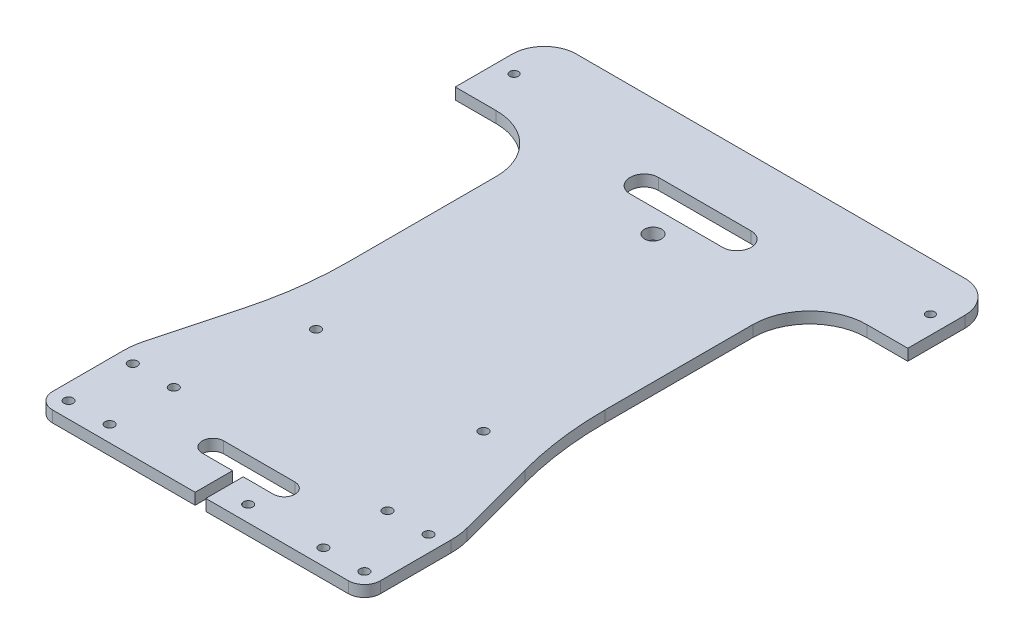
SolidWorks part; units mm, degrees
material "Acrylic (Medium-high impact)"
ref_plane "Front" through (0, 0, 0) normal (0, 0, 1) x (1, 0, 0)
ref_plane "Top" through (0, 0, 0) normal (0, 1, 0) x (1, 0, 0)
ref_plane "Right" through (0, 0, 0) normal (1, 0, 0) x (0, 0, -1)
ref_axis "X" through (-80.9, 0, 0) along (1, 0, 0)
ref_axis "Y" through (0, -50, 0) along (0, 1, 0)
ref_axis "Z" through (0, 0, -80.9) along (0, 0, 1)
sketch "Sketch1" plane through (0, 0, 0) normal (0, 1, 0) x (1, 0, 0)
  line L0 (-46, -160) -> (46, -160)
  line L1 (-46, -160) -> (-46, -133)
  line L2 (-46, -133) -> (-36, -95.6795)
  line L3 (-36, -95.6795) -> (-36, -25)
  line L4 (-36, -25) -> (-63.5, -25)
  line L5 (-63.5, -25) -> (-63.5, 0)
  line L6 (-63.5, 0) -> (63.5, 0)
  line L7 (63.5, 0) -> (63.5, -25)
  line L8 (63.5, -25) -> (36, -25)
  line L9 (36, -25) -> (36, -95.6795)
  line L10 (36, -95.6795) -> (46, -133)
  line L11 (46, -133) -> (46, -160)
  line L12 (0, -160) -> (0, 0) construction
  dimension "D1" = 92
  dimension "D2" = 72
  dimension "D3" = 27
  dimension "D4" = 15
  dimension "D5" = 25
  dimension "D6" = 127
  dimension "D7" = 160
extrude "Boss-Extrude1" add sketch "Sketch1" along normal mid plane 3.175
hole_wizard "M2 Clearance Hole1" positions "Sketch2" profile "Sketch3" hole size "M2" standard "ANSI Metric" end condition up to next
sketch "Sketch2" plane through (0, 1.5875, 0) normal (0, 1, 0) x (1, 0, 0)
  line L0 (-41.5, -155.5) -> (41.5, -155.5) construction
  line L2 (-46, -160) -> (46, -160) construction
  line L3 (-46, -133) -> (-46, -160) construction
  line L4 (46, -160) -> (46, -133) construction
  line L5 (-41.5, -137.5) -> (-41.5, -155.5) construction
  line L8 (41.5, -137.5) -> (41.5, -155.5) construction
  line L9 (-41.5, -137.5) -> (-30, -137.5) construction
  line L10 (-30, -137.5) -> (-30, -155.5) construction
  line L13 (41.5, -137.5) -> (30, -137.5) construction
  line L14 (30, -137.5) -> (30, -155.5) construction
  point P0 (-41.5, -155.5)
  point P2 (41.5, -155.5)
  point P15 (-41.5, -137.5)
  point P17 (41.5, -137.5)
  point P25 (-30, -137.5)
  point P27 (-30, -155.5)
  point P29 (30, -137.5)
  point P31 (30, -155.5)
  dimension "D1" = 4.5
  dimension "D2" = 4.5
  dimension "D3" = 4.5
  dimension "D4" = 18
  dimension "D5" = 60
sketch "Sketch3" plane through (-41.5, 1.5875, 155.5) normal (1, 0, 0) x (0, 0, 1)
  line L0 (0, 0) -> (0, 3.175)
  line L1 (0, 3.175) -> (1.3, 3.175)
  line L2 (1.3, 3.175) -> (1.3, 0)
  line L5 (1.3, 0) -> (0, 0)
  line L11 (0, -6.35) -> (0, 107.95) construction
  dimension "Thru Hole Dia." = 2.6
  dimension "Thru Hole Depth" = 3.175
fillet "Fillet1" radius 4.5 2 edges at (46, 0, 160) (-46, 0, 160)
sketch "Sketch4" plane through (0, 1.5875, 0) normal (0, 1, 0) x (1, 0, 0)
  line L0 (-1.5, -160) -> (-1.5, -149.5)
  line L1 (-41.5, -160) -> (41.5, -160) construction
  line L2 (1.5, -160) -> (1.5, -149.5)
  line L3 (0, 0) -> (0, -146.5) construction
  line L4 (63.5, 0) -> (-63.5, 0) construction
  line L5 (-41.5, -137.5) -> (-41.5, -155.5) construction
  line L6 (-41.5, -146.5) -> (0, -146.5) construction
  line L7 (-1.5, -160) -> (1.5, -160)
  line L8 (-10, -146.5) -> (10, -146.5) construction
  line L9 (-10, -143.5) -> (10, -143.5)
  line L10 (-10, -149.5) -> (-1.5, -149.5)
  line L11 (1.5, -149.5) -> (10, -149.5)
  arc A1 (-10, -143.5) -> (-10, -149.5) centre (-10, -146.5) ccw
  arc A2 (10, -149.5) -> (10, -143.5) centre (10, -146.5) ccw
  point P17 (0, -146.5)
  dimension "D2" = 3
  dimension "D1" = 3
  dimension "D3" = 20
extrude "Cut-Extrude1" cut sketch "Sketch4" against normal up to next
hole_wizard "M2 Clearance Hole3" positions "Sketch5" profile "Sketch6" hole size "M2" standard "ANSI Metric" end condition up to next
sketch "Sketch5" plane through (0, 1.5875, 0) normal (0, 1, 0) x (1, 0, 0)
  line L0 (-24.13, -104.7) -> (24.13, -104.7) construction
  line L2 (-24.13, -104.7) -> (-24.13, -103.43) construction
  line L4 (8.89, -155.5) -> (8.89, -104.7) construction
  line L6 (0, -104.7) -> (0, 0) construction
  line L7 (63.5, 0) -> (-63.5, 0) construction
  line L9 (1.5, -160) -> (41.5, -160) construction
  point P2 (24.13, -104.7)
  point P4 (8.89, -155.5)
  point P20 (-24.13, -103.43)
  dimension "D1" = 48.26
  dimension "D2" = 1.27
  dimension "D3" = 15.24
  dimension "D4" = 50.8
  dimension "D5" = 4.5
sketch "Sketch6" plane through (24.13, 1.5875, 104.7) normal (1, 0, 0) x (0, 0, 1)
  line L0 (0, 0) -> (0, 3.175)
  line L1 (0, 3.175) -> (1.3, 3.175)
  line L2 (1.3, 3.175) -> (1.3, 0)
  line L5 (1.3, 0) -> (0, 0)
  line L11 (0, -6.35) -> (0, 107.95) construction
  dimension "Thru Hole Dia." = 2.6
  dimension "Thru Hole Depth" = 3.175
fillet "Fillet2" radius 9 2 edges at (63.5, 0, 0) (-63.5, 0, 0)
hole_wizard "M2 Clearance Hole2" positions "Sketch7" profile "Sketch8" hole size "M2" standard "ANSI Metric" end condition up to next
sketch "Sketch7" plane through (0, 1.5875, 0) normal (0, 1, 0) x (1, 0, 0)
  line L0 (-58.42, -13.57) -> (58.42, -13.57) construction
  line L2 (0, 0) -> (0, -13.57) construction
  line L3 (54.5, 0) -> (-54.5, 0) construction
  line L5 (-63.5, -25) -> (-36, -25) construction
  point P0 (-58.42, -13.57)
  point P2 (58.42, -13.57)
  dimension "D1" = 116.84
  dimension "D2" = 11.43
sketch "Sketch8" plane through (-58.42, 1.5875, 13.57) normal (1, 0, 0) x (0, 0, 1)
  line L0 (0, 0) -> (0, 3.175)
  line L1 (0, 3.175) -> (1.2, 3.175)
  line L2 (1.2, 3.175) -> (1.2, 0)
  line L5 (1.2, 0) -> (0, 0)
  line L11 (0, -6.35) -> (0, 107.95) construction
  dimension "Thru Hole Dia." = 2.4
  dimension "Thru Hole Depth" = 3.175
fillet "Fillet3" radius 20 2 edges at (46, 0, 133) (-46, 0, 133)
fillet "Fillet4" radius 100 2 edges at (36, 0, 95.6795) (-36, 0, 95.6795)
fillet "Fillet5" radius 16 2 edges at (36, 0, 25) (-36, 0, 25)
sketch "Sketch9" plane through (0, 1.5875, 0) normal (0, 1, 0) x (1, 0, 0)
  line L0 (-13, -22.46) -> (13, -22.46) construction
  line L1 (-13, -18.46) -> (13, -18.46)
  line L2 (-13, -26.46) -> (13, -26.46)
  line L3 (0, 0) -> (0, -22.46) construction
  line L4 (54.5, 0) -> (-54.5, 0) construction
  line L5 (-63.5, -25) -> (-52, -25) construction
  arc A0 (-13, -18.46) -> (-13, -26.46) centre (-13, -22.46) ccw
  arc A1 (13, -26.46) -> (13, -18.46) centre (13, -22.46) ccw
  point P2 (0, -22.46)
  dimension "D1" = 2.54
  dimension "D2" = 26
  dimension "D3" = 8
extrude "Cut-Extrude2" cut sketch "Sketch9" against normal up to next
hole_wizard "M4 Clearance Hole1" positions "Sketch10" profile "Sketch11" hole size "M4" standard "ANSI Metric"
sketch "Sketch10" plane through (0, 1.5875, 0) normal (0, 1, 0) x (1, 0, 0)
  line L0 (0, 0) -> (0, -33) construction
  line L1 (54.5, 0) -> (-54.5, 0) construction
  point P0 (0, -33)
  dimension "D1" = 33
sketch "Sketch11" plane through (0, 1.5875, 33) normal (1, 0, 0) x (0, 0, 1)
  line L0 (0, 0) -> (0, 11.5421)
  line L1 (0, 11.5421) -> (2.4, 10.1)
  line L2 (2.4, 10.1) -> (2.4, 0)
  line L5 (2.4, 0) -> (0, 0)
  line L10 (0, 11.5421) -> (-2.4, 10.1) construction
  line L11 (0, -6.35) -> (0, 107.95) construction
  dimension "Hole Dia." = 4.8
  dimension "Hole Depth" = 10.1
  dimension "Drill Angle" = 118
